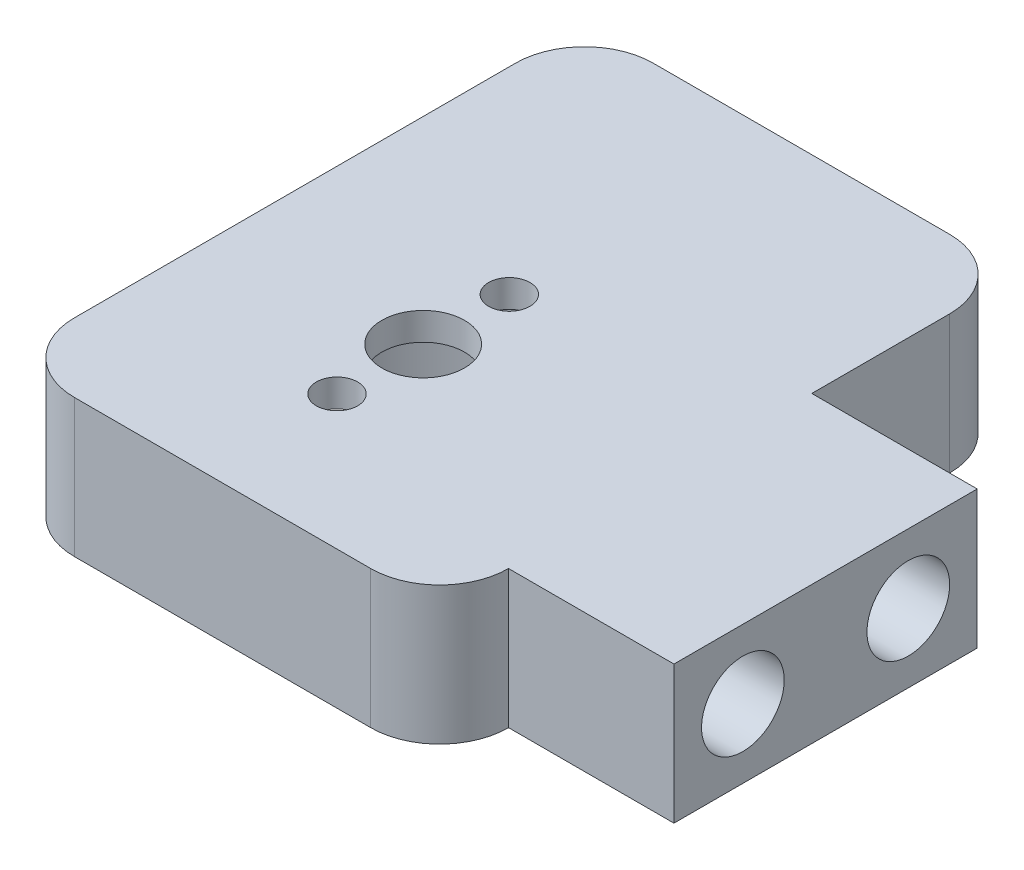
SolidWorks part; units mm, degrees
ref_plane "Front Plane" through (0, 0, 0) normal (0, 0, 1) x (1, 0, 0)
ref_plane "Top Plane" through (0, 0, 0) normal (0, 1, 0) x (1, 0, 0)
ref_plane "Right Plane" through (0, 0, 0) normal (1, 0, 0) x (0, 0, -1)
sketch "Sketch1" plane through (0, 0, 0) normal (0, 1, 0) x (1, 0, 0)
  line L0 (5.5, 11) -> (5.5, 26)
  line L1 (5.5, 11) -> (17.5, 11)
  line L3 (5.5, -11) -> (17.5, -11)
  line L4 (17.5, 11) -> (17.5, -11)
  line L5 (0, 0) -> (17.5, -11) construction
  line L6 (0, 0) -> (17.5, 11) construction
  line L7 (5.5, 26) -> (-26, 26)
  line L8 (-26, 26) -> (-26, -16)
  line L9 (-26, -16) -> (5.5, -16)
  line L10 (5.5, -16) -> (5.5, -11)
  point P0 (0, 0)
  dimension "D1" = 22
  dimension "D2" = 12
  dimension "D3" = 12
  dimension "D4" = 16
  dimension "D5" = 26
  dimension "D6" = 26
extrude "Boss-Extrude1" add sketch "Sketch1" along normal blind 10
sketch "Sketch2" plane through (17.5, 0, 0) normal (1, 0, 0) x (0, 0, -1)
  line L0 (-11, 0) -> (11, 0) construction
  line L1 (-11, 10) -> (-11, 0) construction
  line L2 (11, 10) -> (11, 0) construction
  circle A0 centre (-6, 5) radius 3
  circle A1 centre (6, 5) radius 3
  dimension "D1" = 5
  dimension "D2" = 5
  dimension "D3" = 5
  dimension "D4" = 5
extrude "Cut-Extrude1" cut sketch "Sketch2" against normal blind 10
sketch "Sketch4" plane through (0, 0, 0) normal (0, -1, 0) x (1, 0, 0)
  circle A0 centre (-11.6955, 0) radius 11
extrude "Cut-Extrude3" cut sketch "Sketch4" against normal blind 8
sketch "Sketch5" plane through (0, 8, 0) normal (0, -1, 0) x (-1, 0, 0)
  circle A0 centre (11.6955, 0) radius 3
  circle A1 centre (11.6955, -6.25) radius 1.5
  circle A2 centre (11.6955, 6.25) radius 1.5
  dimension "D1" = 6.25
  dimension "D2" = 3
  dimension "D3" = 6.25
extrude "Cut-Extrude4" cut sketch "Sketch5" against normal blind 8
sketch "Sketch7" plane through (0, 0, 0) normal (0, -1, 0) x (-1, 0, 0)
  line L1 (-0.5, 26) -> (21, 26)
  line L3 (-0.5, 24) -> (21, 24)
  line L5 (-0.5, 24) -> (-0.5, 26)
  line L6 (21, 26) -> (21, 24)
extrude "Boss-Extrude2" add sketch "Sketch7" along normal blind 12
fillet "Fillet1" radius 5 4 edges at (-26, 5, -26) (5.5, 5, -26) (5.5, 5, 16) (-26, 5, 16)
sketch "Sketch8" plane through (0, 0, -24) normal (0, 0, 1) x (1, 0, 0)
  line L0 (-21, -12) -> (-21, 0) construction
  line L1 (0.5, -12) -> (0.5, 0) construction
  line L2 (0.5, 0) -> (-21, 0) construction
  circle A0 centre (-16, -5) radius 3
  circle A1 centre (-4.5, -5) radius 3
  dimension "D1" = 5
  dimension "D2" = 5
  dimension "D3" = 5
  dimension "D4" = 5
extrude "Cut-Extrude5" cut sketch "Sketch8" against normal blind 20
fillet "Fillet2" radius 5 2 edges at (0.5, -12, -25) (-21, -12, -25)
